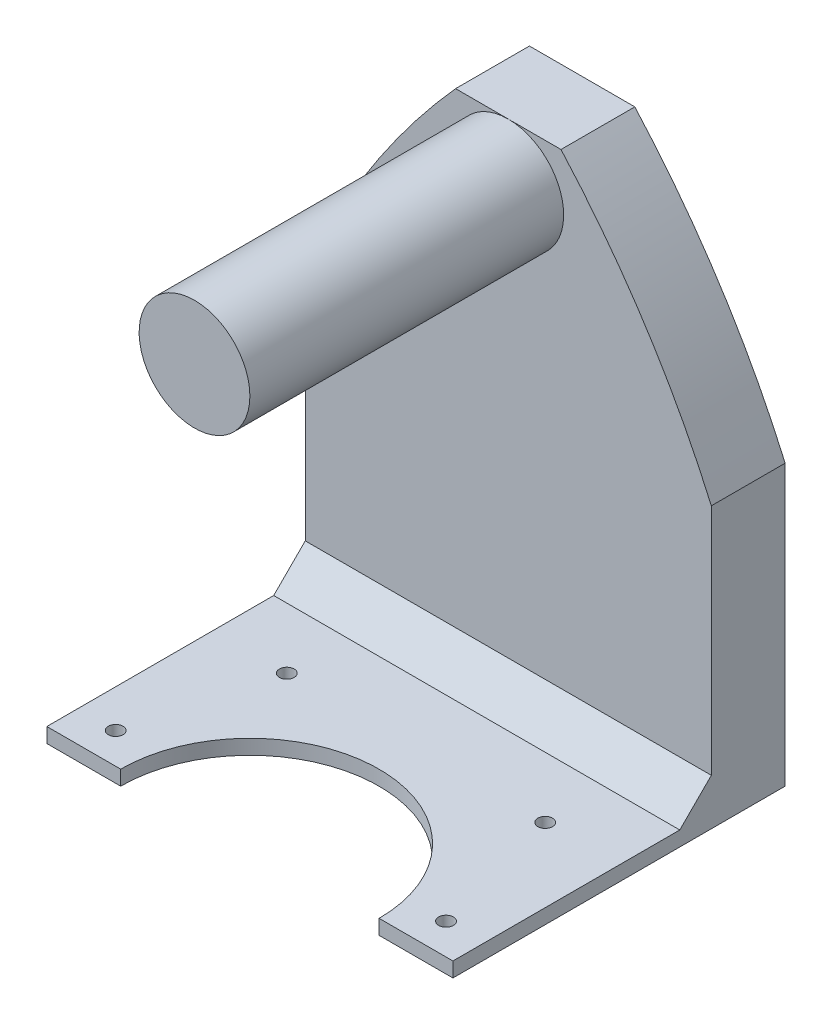
SolidWorks part; units mm, degrees
ref_plane "Front Plane" through (0, 0, 0) normal (0, 0, 1) x (1, 0, 0)
ref_plane "Top Plane" through (0, 0, 0) normal (0, 1, 0) x (1, 0, 0)
ref_plane "Right Plane" through (0, 0, 0) normal (1, 0, 0) x (0, 0, -1)
sketch "Sketch1" plane through (0, 0, 0) normal (0, 1, 0) x (1, 0, 0)
  line L0 (35, -45) -> (55, -45)
  line L1 (-55, -45) -> (-35, -45)
  line L2 (-55, -45) -> (-55, 45)
  line L3 (-55, 45) -> (55, 45)
  line L4 (55, -45) -> (55, 45)
  line L5 (-55, -45) -> (55, 45) construction
  line L6 (-55, 45) -> (55, -45) construction
  arc A0 (-35, -45) -> (35, -45) centre (0, -45) cw
  circle A1 centre (-35, 0) radius 2
  circle A2 centre (35, 0) radius 2
  circle A3 centre (-44.742, -36.6071) radius 2
  circle A4 centre (44.742, -36.6071) radius 2
  point P0 (0, 0)
  dimension "D5" = 35
  dimension "D1" = 90
  dimension "D2" = 110
  dimension "D3" = 20
  dimension "D4" = 20
extrude "Boss-Extrude1" add sketch "Sketch1" along normal blind 4
sketch "Sketch2" plane through (0, 4, 0) normal (0, 1, 0) x (1, 0, 0)
  line L0 (55, -45) -> (55, 45) construction
  line L1 (-55, 45) -> (55, 45)
  line L2 (-55, 45) -> (-55, 25)
  line L3 (-55, 25) -> (55, 25)
  line L4 (55, 45) -> (55, 25)
  dimension "D1" = 20
extrude "Boss-Extrude2" add sketch "Sketch2" along normal blind 135 separate body
sketch "Sketch3" plane through (0, 4, 0) normal (0, 1, 0) x (1, 0, 0)
  line L0 (-55, 45) -> (-55, -45) construction
  line L1 (55, 25) -> (-55, 25)
  line L2 (55, 25) -> (55, 16.4522)
  line L3 (55, 16.4522) -> (-55, 16.4522)
  line L4 (-55, 25) -> (-55, 16.4522)
extrude "Boss-Extrude3" add sketch "Sketch3" along normal blind 10
chamfer "Chamfer1" distance 10 angle 45 1 edges at (0, 14, -16.4522)
sketch "Sketch4" plane through (0, 0, -25) normal (0, 0, 1) x (1, 0, 0)
  line L0 (0, 139) -> (0, 99.3688) construction
  line L1 (-55, 139) -> (55, 139) construction
  circle A0 centre (0, 124) radius 15
extrude "Boss-Extrude4" add sketch "Sketch4" along normal blind 85
sketch "Sketch5" plane through (0, 0, -25) normal (0, 0, 1) x (1, 0, 0)
  line L2 (-55, 139) -> (-55, 12.5478) construction
  line L10 (55, 139) -> (55, 12.5478) construction
  line L11 (0, 139) -> (55, 139) construction
  line L12 (-55, 139) -> (0, 139) construction
  line L13 (-55, 139) -> (-55, 75.7739)
  line L15 (55, 139) -> (55, 75.7739)
  line L16 (14.2766, 139) -> (55, 139)
  line L17 (-55, 139) -> (-14.2766, 139)
  line L23 (0, 139) -> (0, 31.7024) construction
  arc A3 (-14.2766, 139) -> (-55, 75.7739) centre (162.5425, -19.6155) ccw
  arc A4 (14.2766, 139) -> (55, 75.7739) centre (-162.5425, -19.6155) cw
extrude "Cut-Extrude1" cut sketch "Sketch5" against normal blind 85
